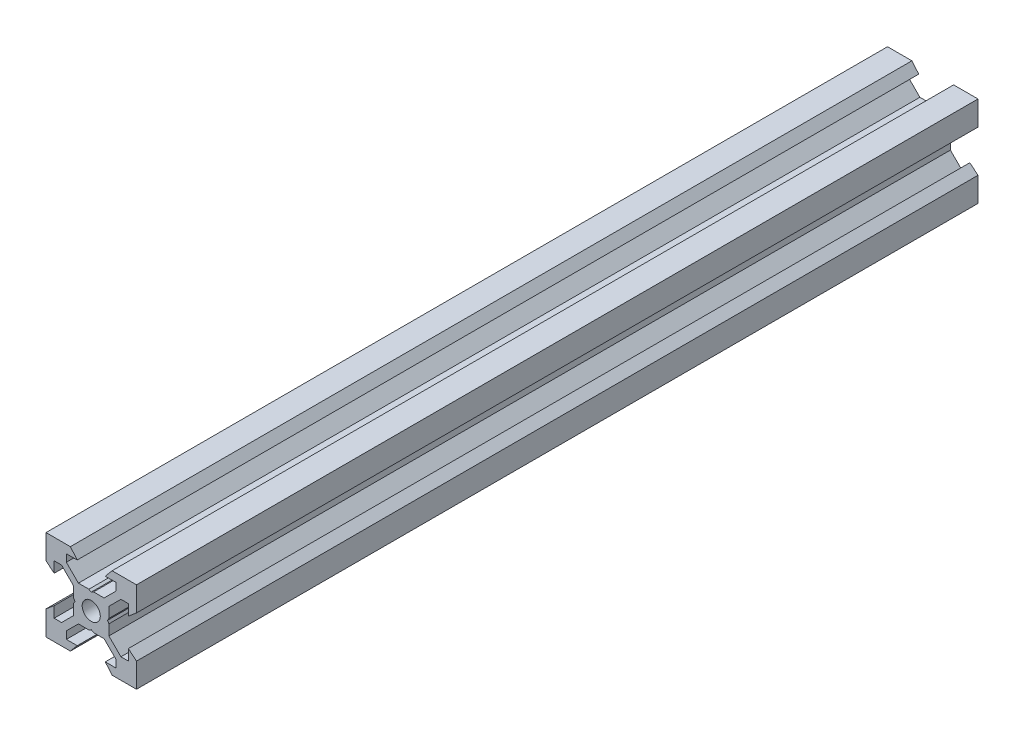
SolidWorks part; units mm, degrees
ref_plane "Front Plane" through (0, 0, 0) normal (0, 0, 1) x (1, 0, 0)
ref_plane "Top Plane" through (0, 0, 0) normal (0, 1, 0) x (1, 0, 0)
ref_plane "Right Plane" through (0, 0, 0) normal (1, 0, 0) x (0, 0, -1)
sketch "Sketch1" plane through (0, 0, 0) normal (0, 0, 1) x (1, 0, 0)
  line L0 (10, 10) -> (4.6104, 10) construction
  line L1 (10, 10) -> (10, 4.6104) construction
  line L2 (10, -10) -> (10, -4.6104) construction
  line L3 (10, -10) -> (4.6104, -10) construction
  line L4 (10, 10) -> (10, 4.6104)
  line L5 (6.5607, 5.5) -> (8.2, 5.5)
  line L6 (5.5, 8.2) -> (5.5, 6.5607)
  line L7 (10, 10) -> (4.6104, 10)
  line L8 (10, 10) -> (10, 4.6104)
  line L9 (6.5607, 5.5) -> (3.9, 2.8393)
  line L10 (5.5, 6.5607) -> (2.8393, 3.9)
  line L11 (10, 4.6104) -> (8.2, 3.1)
  line L12 (4.6104, 10) -> (3.1, 8.2)
  line L13 (8.2, 3.1) -> (8.2, 5.5)
  line L14 (3.1, 8.2) -> (5.5, 8.2)
  line L15 (-6.5607, 5.5) -> (-8.2, 5.5)
  line L16 (6.5607, -5.5) -> (8.2, -5.5)
  line L17 (3.1, -8.2) -> (5.5, -8.2)
  line L18 (8.2, -3.1) -> (8.2, -5.5)
  line L19 (4.6104, -10) -> (3.1, -8.2)
  line L20 (10, -4.6104) -> (8.2, -3.1)
  line L21 (0.5196, -3.9) -> (0, -3.6)
  line L22 (0.5196, 3.9) -> (0, 3.6)
  line L23 (3.6, 0) -> (3.9, -0.5196)
  line L24 (3.9, 0.5196) -> (3.6, 0)
  line L25 (3.9, 0.5196) -> (3.9, 2.8393)
  line L26 (2.8393, 3.9) -> (0.5196, 3.9)
  line L27 (3.9, -2.8393) -> (3.9, -0.5196)
  line L28 (2.8393, -3.9) -> (0.5196, -3.9)
  line L29 (5.5, -6.5607) -> (2.8393, -3.9)
  line L30 (6.5607, -5.5) -> (3.9, -2.8393)
  line L31 (10, -10) -> (10, -4.6104)
  line L32 (10, -10) -> (4.6104, -10)
  line L33 (5.5, -8.2) -> (5.5, -6.5607)
  line L34 (-6.5607, -5.5) -> (-8.2, -5.5)
  line L35 (10, -10) -> (10, -4.6104)
  line L36 (0, 0) -> (0, 8.2) construction
  line L37 (-10, -10) -> (-4.6104, -10) construction
  line L38 (-10, -10) -> (-10, -4.6104) construction
  line L39 (-10, 10) -> (-10, 4.6104) construction
  line L40 (-10, 10) -> (-4.6104, 10) construction
  line L41 (-10, -10) -> (-10, -4.6104)
  line L43 (-5.5, -8.2) -> (-5.5, -6.5607)
  line L44 (-10, -10) -> (-4.6104, -10)
  line L45 (-10, -10) -> (-10, -4.6104)
  line L46 (-6.5607, -5.5) -> (-3.9, -2.8393)
  line L47 (-5.5, -6.5607) -> (-2.8393, -3.9)
  line L48 (-2.8393, -3.9) -> (-0.5196, -3.9)
  line L49 (-3.9, -2.8393) -> (-3.9, -0.5196)
  line L50 (-2.8393, 3.9) -> (-0.5196, 3.9)
  line L51 (-3.9, 0.5196) -> (-3.9, 2.8393)
  line L52 (-3.9, 0.5196) -> (-3.6, 0)
  line L53 (-3.6, 0) -> (-3.9, -0.5196)
  line L54 (-0.5196, 3.9) -> (0, 3.6)
  line L55 (-0.5196, -3.9) -> (0, -3.6)
  line L56 (-10, -4.6104) -> (-8.2, -3.1)
  line L57 (-4.6104, -10) -> (-3.1, -8.2)
  line L58 (-8.2, -3.1) -> (-8.2, -5.5)
  line L59 (-3.1, -8.2) -> (-5.5, -8.2)
  line L60 (-10, -10) -> (10, -10) construction
  line L61 (-10, -10) -> (-10, 10) construction
  line L62 (-3.1, 8.2) -> (-5.5, 8.2)
  line L63 (-8.2, 3.1) -> (-8.2, 5.5)
  line L64 (-4.6104, 10) -> (-3.1, 8.2)
  line L65 (-10, 4.6104) -> (-8.2, 3.1)
  line L66 (-5.5, 6.5607) -> (-2.8393, 3.9)
  line L67 (-6.5607, 5.5) -> (-3.9, 2.8393)
  line L68 (-10, 10) -> (-10, 4.6104)
  line L69 (-10, 10) -> (-4.6104, 10)
  line L70 (-5.5, 8.2) -> (-5.5, 6.5607)
  line L71 (-10, 10) -> (10, 10) construction
  line L72 (-10, 10) -> (-10, 4.6104)
  line L73 (10, -10) -> (10, 10) construction
  line L74 (-10, -10) -> (10, 10) construction
  line L75 (-10, 10) -> (10, -10) construction
  circle A0 centre (0, 0) radius 2
  dimension "D7" = 4
  dimension "D1" = 20
  dimension "D2" = 5.3896
  dimension "D3" = 4.5
  dimension "D4" = 50
  dimension "D5" = 1.8
  dimension "D6" = 1.5104
  dimension "D8" = 5.5
  dimension "D9" = 120
  dimension "D10" = 0.3
  dimension "D11" = 2.3197
  dimension "D12" = 7.8
  dimension "D13" = 7.8
  dimension "D14" = 1.5
  dimension "D15" = 2.6607
extrude "Boss-Extrude1" add sketch "Sketch1" along normal mid plane 186 contours L70 L62 L64 L69 L68 L65 L63 L15 L67 L51 L52 L53 L49 L46 L34 L58 L56 L41 L44 L57 L59 L43 L47 L48 L55 L21 L28 L29 L33 L17 L19 L32 L31 L20 L18 L16 L30 L27 L23 L24 L25 L9 L5 L13 L11 L4 L7 L12 L14 L6 L10 region at (9.7172, 7.3052, 0)
